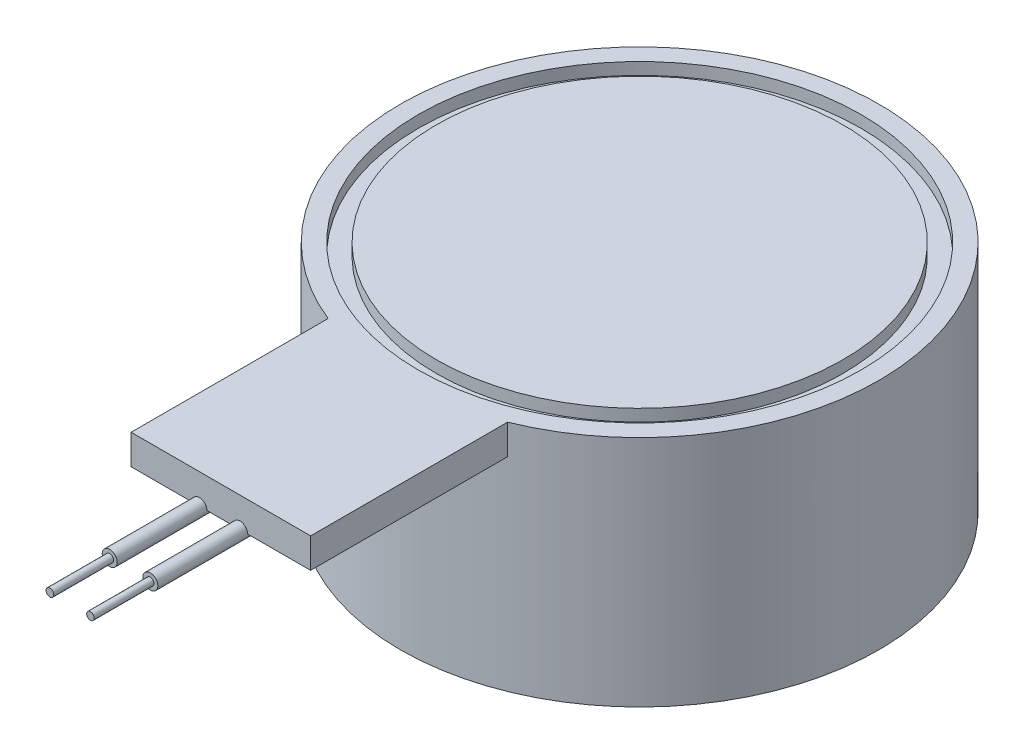
SolidWorks part; units mm, degrees
ref_plane "Front Plane" through (0, 0, 0) normal (0, 0, 1) x (1, 0, 0)
ref_plane "Top Plane" through (0, 0, 0) normal (0, 1, 0) x (1, 0, 0)
ref_plane "Right Plane" through (0, 0, 0) normal (1, 0, 0) x (0, 0, -1)
sketch "Sketch1" plane through (0, 0, 0) normal (0, 1, 0) x (1, 0, 0)
  circle A5 centre (2.013, 4.989) radius 4
  circle A6 centre (2.013, 4.989) radius 3.5
  dimension "D1" = 8
  dimension "D2" = 7
extrude "Boss-Extrude3" add sketch "Sketch1" against normal blind 3.4 contours A5
sketch "Sketch3" plane through (0, 0, 0) normal (0, 1, 0) x (1, 0, 0)
  circle A0 centre (2.013, 4.989) radius 4
  dimension "D1" = 8
extrude "Boss-Extrude5" add sketch "Sketch3" along normal blind 0.5
sketch "Sketch5" plane through (0, 0.5, 0) normal (0, 1, 0) x (1, 0, 0)
  line L0 (2.013, 4.989) -> (6.013, 4.989) construction
  line L1 (2.013, 4.989) -> (-1.987, 4.989) construction
  line L2 (2.013, 4.989) -> (2.013, 0.989) construction
  line L3 (2.013, 4.989) -> (2.013, 8.989) construction
  line L4 (0.513, 1.2809) -> (0.513, -2.011)
  line L5 (0.513, -2.011) -> (3.513, -2.011)
  line L6 (3.513, -2.011) -> (3.513, 1.2809)
  line L7 (2.013, -2.011) -> (2.013, -1.8789) construction
  circle A1 centre (2.013, 4.989) radius 4 construction
  circle A2 centre (2.013, 4.989) radius 4
  arc A3 (0.513, 1.2809) -> (-1.9148, 5.7454) centre (2.013, 4.989) ccw
  arc A4 (0.513, 1.2809) -> (3.7558, 1.3886) centre (2.013, 4.989) ccw
  circle M6 centre (2.013, 4.989) radius 4
  dimension "D1" = 1.5
  dimension "D2" = 1.5
  dimension "D3" = 7
  dimension "D4" = 0
extrude "Boss-Extrude6" add sketch "Sketch5" against normal blind 0.5 contours L5 L6 A3 L4 M6 region at (2.013, 0.5, 0.4619)
sketch "Sketch8" plane through (0, 0, 2.011) normal (0, 0, 1) x (1, 0, 0)
  line L0 (2.138, -2) -> (2.138, 0) construction
  line L3 (0.513, 0) -> (3.513, 0) construction
  line L5 (2.763, -1) -> (1.263, -1) construction
  circle A0 centre (2.3342, 0) radius 0.125
  circle A1 centre (1.6547, 0) radius 0.125
  dimension "D1" = 0.25
  dimension "D2" = 0.25
  dimension "D3" = 0
  dimension "D4" = 0
extrude "Boss-Extrude10" add sketch "Sketch8" along normal blind 1.5
sketch "Sketch9" plane through (0, 0, 3.511) normal (0, 0, 1) x (1, 0, 0)
  circle A0 centre (2.3322, 0) radius 0.0625
  circle A1 centre (1.6547, 0) radius 0.065
  dimension "D1" = 0.125
  dimension "D2" = 0.13
  dimension "D3" = 0
extrude "Boss-Extrude11" add sketch "Sketch9" along normal blind 1
fillet "Congé1" radius 1 2 edges at (2.3342, 0, 2.011) (1.6547, 0, 2.011)
sketch "Esquisse1" plane through (0, 0.5, 0) normal (0, 1, 0) x (1, 0, 0)
  circle A0 centre (2.013, 4.989) radius 3.7
  circle A1 centre (2.013, 4.989) radius 3.4
extrude "Enlèv. mat.-Extru.1" cut sketch "Esquisse1" against normal blind 0.2
